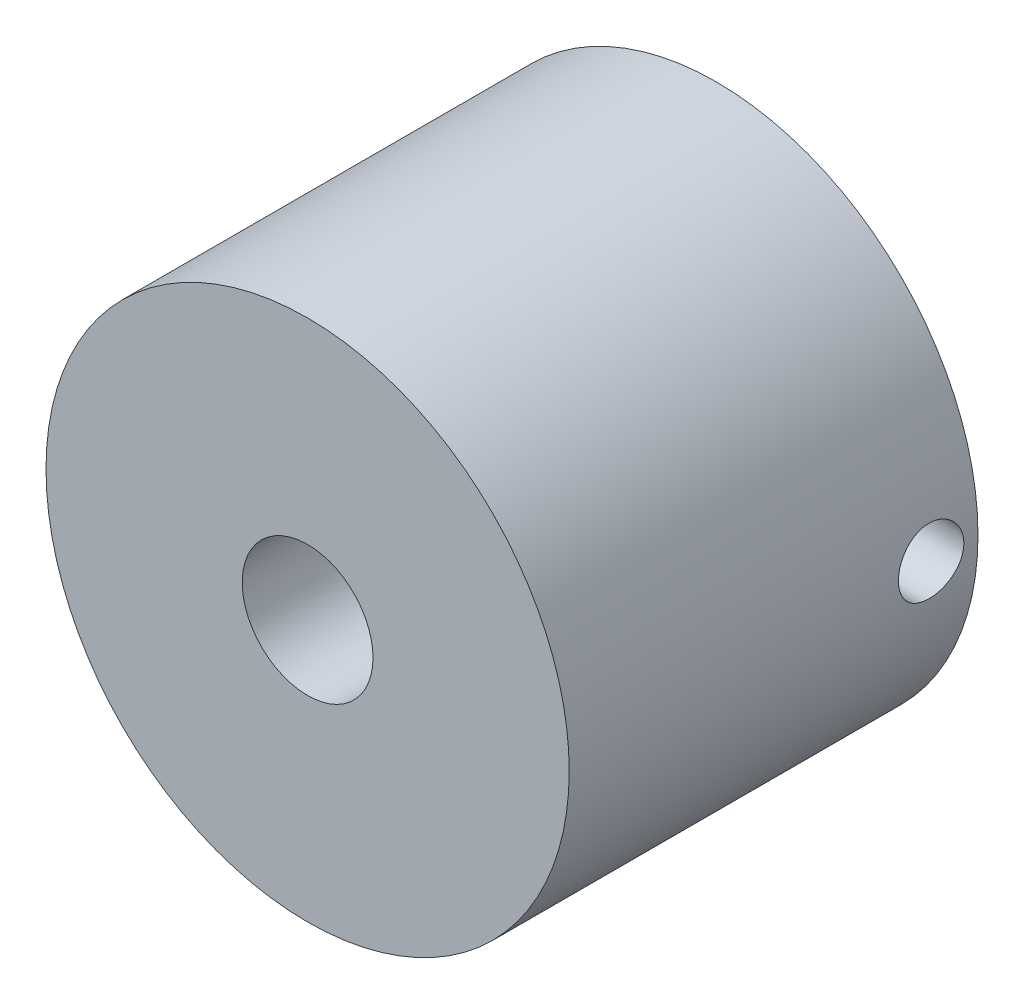
SolidWorks part; units mm, degrees
ref_plane "Front Plane" through (0, 0, 0) normal (0, 0, 1) x (1, 0, 0)
ref_plane "Top Plane" through (0, 0, 0) normal (0, 1, 0) x (1, 0, 0)
ref_plane "Right Plane" through (0, 0, 0) normal (1, 0, 0) x (0, 0, -1)
sketch "Sketch1" plane through (0, 0, 0) normal (0, 0, 1) x (1, 0, 0)
  circle A0 centre (0, 0) radius 6
  circle A1 centre (0, 0) radius 16
extrude "Boss-Extrude1" add sketch "Sketch1" along normal blind 14
sketch "Sketch2" plane through (0, 0, 14) normal (0, 0, 1) x (1, 0, 0)
  circle A0 centre (0, 0) radius 3
  circle A1 centre (0, 0) radius 6
extrude "Boss-Extrude2" add sketch "Sketch2" against normal blind 8
thread "Thread1" pitch 0.3175 method extrude profile "Thread Profile2" start angle 0, offset 0, length 0, pitch 1, diameter 6
ref_plane "Plane3" through (-3, 0, 14) normal (0, -1, 0) x (-1, 0, 0)
sketch "Thread Profile2" plane through (-3, 0, 14) normal (0, -1, 0) x (-1, 0, 0)
  line L0 (0, 0) -> (0, 0.3175) construction
  line L11 (0, 0) -> (0, 0.2778)
  line L12 (0, 0.2778) -> (-0.1719, 0.1786)
  line L13 (-0.1719, 0.1786) -> (-0.1719, 0.0992)
  line L15 (-0.1719, 0.0992) -> (0, 0)
  line L17 (-0.1719, 0.1389) -> (0, 0.1389) construction
  point P2 (0, 0)
  dimension "Pitch" = 0.3175
  dimension "Profile_Angle" = 60
  dimension "Profile_Land" = 0.0794
  dimension "Profile_Height" = 0.1719
sketch "Sketch14" plane through (0, 0, 0) normal (1, 0, 0) x (0, 0, -1)
  circle A0 centre (-2.8662, 0) radius 2
  point P2 (-2.8662, 0)
extrude "Cut-Extrude1" cut sketch "Sketch14" along normal through all both and the other way through all
sketch "Sketch15" plane through (0, 0, 0) normal (0, 0, -1) x (-1, 0, 0)
  circle A0 centre (0, 0) radius 16 construction
  point P0 (-16, 0)
ref_plane "Plane4" [suppressed] through (16, 0, 0) normal (1, 0, 0) x (0, 0, -1)
thread "Thread2" [suppressed] pitch 0.3175 start angle 0, offset 0, length 10, pitch 0.3175, diameter 4
ref_plane "Plane5" through (16, 0, 0.8662) normal (0, -1, 0) x (0, 0, -1)
sketch "Thread Profile3" plane through (16, 0, 0.8662) normal (0, -1, 0) x (0, 0, -1)
  line L0 (0, 0) -> (0, 0.3175) construction
  line L11 (0, 0) -> (0, 0.2778)
  line L12 (0, 0.2778) -> (-0.1719, 0.1786)
  line L13 (-0.1719, 0.1786) -> (-0.1719, 0.0992)
  line L15 (-0.1719, 0.0992) -> (0, 0)
  line L17 (-0.1719, 0.1389) -> (0, 0.1389) construction
  point P2 (0, 0)
  dimension "Pitch" = 0.3175
  dimension "Profile_Angle" = 60
  dimension "Profile_Land" = 0.0794
  dimension "Profile_Height" = 0.1719
sketch "Sketch18" plane through (0, 0, 0) normal (0, 0, -1) x (-1, 0, 0)
  circle A0 centre (0, 0) radius 16 construction
  point P0 (16, 0)
ref_plane "Plane6" [suppressed] through (-16, 0, 0) normal (1, 0, 0) x (0, 0, -1)
thread "Thread3" [suppressed] pitch 0.3175 start angle 0, offset 0, length 10, pitch 0.3175, diameter 4
ref_plane "Plane7" through (-16, 0, 0.8662) normal (0, -1, 0) x (0, 0, -1)
sketch "Thread Profile4" plane through (-16, 0, 0.8662) normal (0, -1, 0) x (0, 0, -1)
  line L0 (0, 0) -> (0, 0.3175) construction
  line L11 (0, 0) -> (0, 0.2778)
  line L12 (0, 0.2778) -> (-0.1719, 0.1786)
  line L13 (-0.1719, 0.1786) -> (-0.1719, 0.0992)
  line L15 (-0.1719, 0.0992) -> (0, 0)
  line L17 (-0.1719, 0.1389) -> (0, 0.1389) construction
  point P2 (0, 0)
  dimension "Pitch" = 0.3175
  dimension "Profile_Angle" = 60
  dimension "Profile_Land" = 0.0794
  dimension "Profile_Height" = 0.1719
sketch "Sketch21" plane through (0, 0, 14) normal (0, 0, 1) x (1, 0, 0)
  circle A0 centre (0, 0) radius 16
  circle A1 centre (0, 0) radius 4
extrude "Boss-Extrude3" add sketch "Sketch21" along normal blind 11
